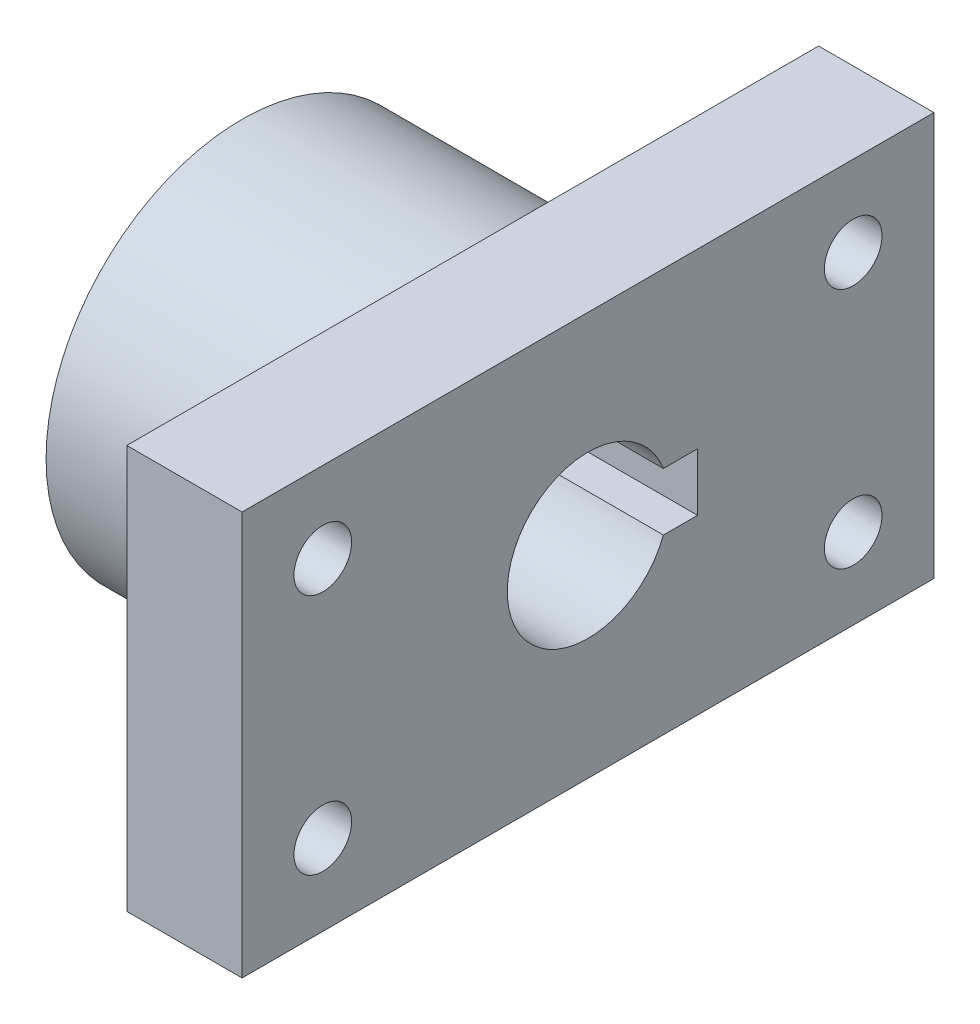
SolidWorks part; units mm, degrees
material "Plain Carbon Steel"
ref_plane "Front Plane" through (0, 0, 0) normal (0, 0, 1) x (1, 0, 0)
ref_plane "Top Plane" through (0, 0, 0) normal (0, 1, 0) x (1, 0, 0)
ref_plane "Right Plane" through (0, 0, 0) normal (1, 0, 0) x (0, 0, -1)
sketch "Sketch1" plane through (0, 0, 0) normal (1, 0, 0) x (0, 0, -1)
  line L1 (30, -17.5) -> (-30, -17.5)
  line L2 (30, -17.5) -> (30, 17.5)
  line L3 (30, 17.5) -> (-30, 17.5)
  line L4 (-30, -17.5) -> (-30, 17.5)
  line L5 (30, -17.5) -> (-30, 17.5) construction
  line L6 (30, 17.5) -> (-30, -17.5) construction
  point P0 (0, 0)
  dimension "D1" = 60
  dimension "D2" = 35
extrude "Boss-Extrude1" add sketch "Sketch1" along normal blind 30
sketch "Sketch2" plane through (30, 0, 0) normal (1, 0, 0) x (0, 0, -1)
  line L7 (4.5, -2.5) -> (9.5, -2.5)
  line L8 (4.5, -2.5) -> (4.5, 2.5)
  line L9 (4.5, 2.5) -> (9.5, 2.5)
  line L10 (9.5, -2.5) -> (9.5, 2.5)
  line L11 (4.5, -2.5) -> (9.5, 2.5) construction
  line L12 (4.5, 2.5) -> (9.5, -2.5) construction
  circle A0 centre (0, 0) radius 7
  point P3 (0, 7)
  point P8 (7, 0)
  dimension "D1" = 14
  dimension "D2" = 5
extrude "Cut-Extrude1" cut sketch "Sketch2" against normal through all contours L9 A0 L7 L8 | L7 A0 L9 L8 | A0 L7 L10 L9 region at (30, 0, -5.6781) region at (30, 0, 0.4688) region at (30, 0, -8.1706)
hole_wizard "Ø5.0 (5) Diameter Hole1" positions "Sketch5" profile "Sketch4" hole size "Ø5.0" standard "ISO" end condition through all
sketch "Sketch5" plane through (0, 0, 0) normal (-1, 0, 0) x (0, 0, 1)
  line L0 (-23, 17.5) -> (-23, 10.5) construction
  line L1 (-30, 17.5) -> (30, 17.5) construction
  line L2 (-23, 10.5) -> (-23, -10.5) construction
  line L3 (-23, -10.5) -> (-23, -17.5) construction
  line L4 (30, -17.5) -> (-30, -17.5) construction
  line L6 (-30, -17.5) -> (-30, 17.5) construction
  point P0 (-23, 10.5)
  point P2 (-23, -10.5)
  dimension "D1" = 7
  dimension "D2" = 7
sketch "Sketch4" plane through (0, 10.5, -23) normal (0, 1, 0) x (0, 0, 1)
  line L0 (0, 0) -> (0, 30)
  line L1 (0, 30) -> (2.5, 30)
  line L2 (2.5, 30) -> (2.5, 0)
  line L5 (2.5, 0) -> (0, 0)
  line L11 (0, -6.35) -> (0, 107.95) construction
  dimension "Thru Hole Dia." = 5
  dimension "Thru Hole Depth" = 30
mirror "Mirror1" about plane through (0, 0, 0) normal (0, 0, 1) of "Ø5.0 (5) Diameter Hole1"
sketch "Sketch6" plane through (0, 0, 0) normal (-1, 0, 0) x (0, 0, 1)
  line L1 (-30, 17.5) -> (30, 17.5)
  line L2 (-30, 17.5) -> (-30, -17.5)
  line L3 (-30, -17.5) -> (30, -17.5)
  line L4 (30, 17.5) -> (30, -17.5)
  circle A0 centre (0, 0) radius 17
  dimension "D1" = 34
extrude "Cut-Extrude2" cut sketch "Sketch6" against normal offset from surface (20 mm away) 10 up to face at (30, 0, 0)
